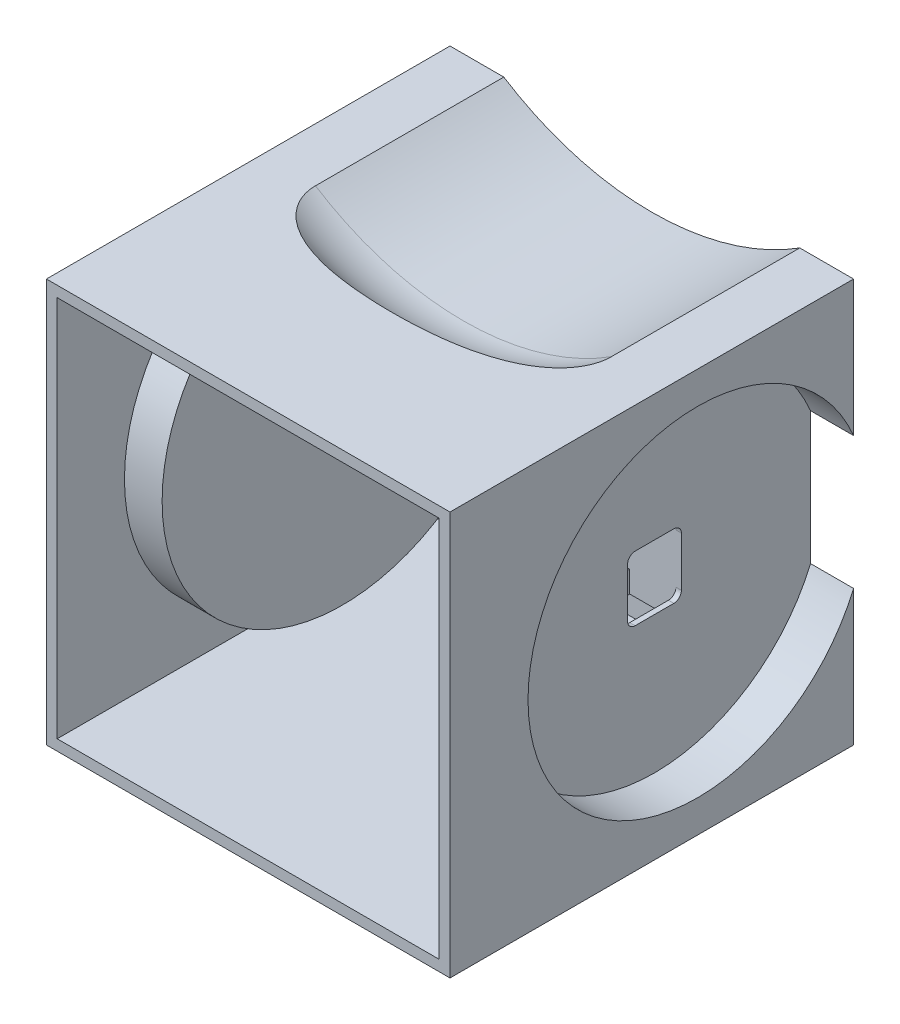
SolidWorks part; units mm, degrees
ref_plane "Plano frontal" through (0, 0, 0) normal (0, 0, 1) x (1, 0, 0)
ref_plane "Plano superior" through (0, 0, 0) normal (0, 1, 0) x (1, 0, 0)
ref_plane "Plano direito" through (0, 0, 0) normal (1, 0, 0) x (0, 0, -1)
sketch "Esboço1" plane through (0, 0, 0) normal (0, 0, 1) x (1, 0, 0)
  line L0 (-37.8091, -28.8009) -> (37.1909, -28.8009)
  line L1 (-37.8091, -28.8009) -> (-37.8091, 46.1991)
  line L2 (37.1909, -28.8009) -> (37.1909, 46.1991)
  line L3 (37.1909, 46.1991) -> (-37.8091, 46.1991)
  line L4 (-37.8091, 46.1991) -> (-27.8091, 46.1991)
  line L5 (37.1909, 46.1991) -> (27.1909, 46.1991)
  line L6 (-0.3091, 46.1991) -> (-0.3091, 38.1991)
  line L7 (-0.3091, 38.1991) -> (-0.3091, 36.1991)
  line L8 (-37.8091, 8.6991) -> (-35.8091, 8.6991)
  line L9 (-0.3091, -28.8009) -> (-0.3091, -26.8009)
  line L10 (31.7818, 46.1991) -> (31.7818, 44.1991)
  line L11 (37.1909, 41.0812) -> (35.1909, 41.0812)
  line L13 (-35.8091, -26.8009) -> (35.1909, -26.8009)
  line L14 (-35.8091, -26.8009) -> (-35.8091, 44.1991)
  line L15 (-35.8091, 44.1991) -> (35.1909, 44.1991)
  line L16 (35.1909, -26.8009) -> (35.1909, 44.1991)
  circle A0 centre (-0.3091, 89.4647) radius 51.2656
  circle A1 centre (-0.3091, 89.4647) radius 53.2656
  spline S0 degree 2 poles (-27.8091, 46.1991) (-0.3091, 30.1991) (27.1909, 46.1991) knots 0 0 0 1 1 1
  dimension "D7" = 102.5312
  dimension "D1" = 75
  dimension "D2" = 75
  dimension "D3" = 10
  dimension "D4" = 10
  dimension "D5" = 8
  dimension "D6" = 2
  dimension "D8" = 2
  dimension "D9" = 2
  dimension "D10" = 2
  dimension "D11" = 2
extrude "Ressalto-extrusão2" add sketch "Esboço1" along normal blind 50 contours A1 L4 L1 L8 L14 L15 | L3 A1 L15 A0 | L15 A1 L7 A0 | L7 A1 L15 A0 | L15 A1 L3 A0 | A1 L15 L10 L5 | L16 L11 L2 L3 L10 L15 | L16 L13 L9 L0 L2 L11 | L13 L14 L8 L1 L0 L9 region at (-37.2787, -10.0509, 0) region at (0.484, -27.8009, 0) region at (-36.2648, 29.8474, 0) region at (35.1096, 44.2634, 0) region at (-27.9997, 45.1797, 0) region at (-13.7006, 39.5358, 0) region at (30.3906, 44.9982, 0) region at (27.3815, 45.1797, 0) region at (13.0825, 39.5358, 0)
sketch "Esboço3" plane through (0, 0, 50) normal (0, 0, 1) x (1, 0, 0)
  line L0 (-37.8091, 46.1991) -> (-37.8091, -28.8009)
  line L1 (-37.8091, -28.8009) -> (37.1909, -28.8009)
  line L2 (37.1909, -28.8009) -> (37.1909, 46.1991)
  line L3 (37.1909, 46.1991) -> (-37.8091, 46.1991)
  line L4 (-35.8091, 44.1991) -> (-35.8091, -26.8009)
  line L5 (-35.8091, -26.8009) -> (35.1909, -26.8009)
  line L6 (35.1909, -26.8009) -> (35.1909, 44.1991)
  line L7 (35.1909, 44.1991) -> (-35.8091, 44.1991)
extrude "Ressalto-extrusão3" add sketch "Esboço3" along normal blind 25
sketch "Esboço4" plane through (0, 0, 50) normal (0, 0, 1) x (1, 0, 0)
  line L0 (-28.3849, 44.1991) -> (27.7667, 44.1991)
  circle A1 centre (-0.3091, 89.4647) radius 53.2656
  arc M3 (-28.3849, 44.1991) -> (27.7667, 44.1991) centre (-0.3091, 89.4647) ccw
  line M4 (27.7667, 44.1991) -> (23.7572, 44.1991)
  arc M5 (23.7572, 44.1991) -> (-24.3754, 44.1991) centre (-0.3091, 89.4647) cw
  line M6 (-24.3754, 44.1991) -> (-28.3849, 44.1991)
extrude "Ressalto-extrusão6" add sketch "Esboço4" along normal blind 2 contours L0 M5 | M6 M3 M4 M5 region at (-26.3801, 43.6319, 50) region at (-0.3091, 41.7866, 50)
fillet "Filete2" radius 15 1 edges at (-0.3091, 38.1991, 50)
sketch "Esboço5" plane through (0, 0, 0) normal (0, 0, -1) x (-1, 0, 0)
  line L0 (-27.1909, 46.1991) -> (-37.1909, 46.1991)
  line L1 (-37.1909, 46.1991) -> (-37.1909, -28.8009)
  line L2 (-37.1909, -28.8009) -> (37.8091, -28.8009)
  line L3 (37.8091, -28.8009) -> (37.8091, 46.1991)
  line L4 (37.8091, 46.1991) -> (27.8091, 46.1991)
  circle A0 centre (0.3091, 89.4647) radius 51.2656
  line M7 (28.3849, 44.1991) -> (35.8091, 44.1991)
  line M8 (35.8091, 44.1991) -> (35.8091, -26.8009)
  line M9 (35.8091, -26.8009) -> (-35.1909, -26.8009)
  line M10 (-35.1909, -26.8009) -> (-35.1909, 44.1991)
  line M11 (-35.1909, 44.1991) -> (-27.7667, 44.1991)
  arc M12 (-27.7667, 44.1991) -> (28.3849, 44.1991) centre (0.3091, 89.4647) ccw
extrude "Ressalto-extrusão7" add sketch "Esboço5" against normal blind 2 contours M7 M12 M11 M10 M9 M8 region at (-0.3091, 6.6255, 0)
sketch "Esboço6" plane through (-37.8091, 0, 0) normal (-1, 0, 0) x (0, 0, 1)
  line L0 (0, 46.1991) -> (0, -28.8009)
  line L3 (0, 8.6991) -> (-1, 8.6991)
  line L4 (-1, 8.6991) -> (59, 8.6991)
  circle A0 centre (29, 8.6991) radius 30
  circle A1 centre (29, 8.6991) radius 31.5
  line M5 (0, 46.1991) -> (0, -28.8009)
  dimension "D3" = 1.5
  dimension "D1" = 60
  dimension "D2" = 1
extrude "Corte-extrusão2" cut sketch "Esboço6" against normal blind 8 and the other way through all contours L4 A0 L0 | L0 A0 L4 | A1 L0 A0 M5 | L0 A1 A0 M5 | L3 A0 L0 | L0 A0 L3 region at (-37.8091, 38.7118, 35.101) region at (-37.8091, 8.6991, -1.203) region at (-37.8091, 21.4674, 29.1072) region at (-37.8091, 11.586, -0.4006) region at (-37.8091, -4.0692, 29.1072) region at (-37.8091, 5.8121, -0.4006)
sketch "Esboço7" plane through (35.1909, 0, 0) normal (-1, 0, 0) x (0, 0, 1)
  line L0 (2, 24.924) -> (2, -7.5259)
  circle A1 centre (29, 8.6991) radius 31.5
  line M2 (2, 44.1991) -> (2, -26.8009)
extrude "Corte-extrusão4" cut sketch "Esboço7" along normal blind 6 and the other way through all contours A1 M2 | A1 M2 region at (35.1909, 8.6991, 29.9434) region at (35.1909, 8.6991, 0.1885)
sketch "Esboço8" plane through (35.1909, 0, 0) normal (-1, 0, 0) x (0, 0, 1)
  line L0 (2, 24.924) -> (2, 28.5296)
  line L1 (2, -7.5259) -> (2, -11.1315)
  circle A0 centre (29, 8.6991) radius 31.5
  circle A1 centre (29, 8.6991) radius 33.5
  arc M2 (2, 24.924) -> (2, -7.5259) centre (29, 8.6991) cw
  line M3 (2, -7.5259) -> (2, -26.8009)
  line M7 (2, 44.1991) -> (2, 24.924)
  dimension "D1" = 2
extrude "Ressalto-extrusão8" add sketch "Esboço8" along normal blind 6 contours A1 M3 M7 M2 region at (35.1909, 26.7268, 2.9027)
sketch "Esboço9" plane through (-35.8091, 0, 0) normal (1, 0, 0) x (0, 0, -1)
  line L0 (-2, 24.924) -> (-2, 28.5296)
  line L1 (-2, -7.5259) -> (-2, -11.1315)
  line L2 (-2, -7.5259) -> (-2, -26.8009) construction
  circle A0 centre (-29, 8.6991) radius 31.5
  circle A1 centre (-29, 8.6991) radius 33.5
  arc M2 (-2, -7.5259) -> (-2, 24.924) centre (-29, 8.6991) cw
  line M3 (-2, 24.924) -> (-2, 44.1991)
  line M7 (-2, -26.8009) -> (-2, -7.5259)
  dimension "D1" = 2
extrude "Ressalto-extrusão9" add sketch "Esboço9" along normal blind 6 contours A1 M3 M7 M2 region at (-35.8091, 8.6991, 61.4027)
sketch "Esboço20" plane through (29.1909, 0, 0) normal (-1, 0, 0) x (0, 0, 1)
  line L0 (0, 20.9974) -> (0, -3.5993)
  line L1 (0, 20.9974) -> (0, 29.956)
  line L2 (0, -3.5993) -> (0, -14.1953)
  circle A0 centre (29, 8.6991) radius 33.5
  line M1 (2, -7.5259) -> (2, -11.1315)
  arc M2 (2, -11.1315) -> (2, 28.5296) centre (29, 8.6991) ccw
  line M3 (2, 28.5296) -> (2, 24.924)
  arc M4 (2, 24.924) -> (2, -7.5259) centre (29, 8.6991) cw
extrude "Ressalto-extrusão22" add sketch "Esboço20" along normal blind 1 contours M4 M1 M2 M3 | A0 L1 L0 L2 M3 M1 M4 region at (29.1909, 8.6991, 29.2565) region at (29.1909, 39.6748, 39.1531)
sketch "Esboço21" plane through (-29.8091, 0, 0) normal (1, 0, 0) x (0, 0, -1)
  line L0 (0, -2.839) -> (0, -10.7319)
  line L1 (0, 20.9974) -> (0, -3.5993) construction
  line L2 (0, 18.5479) -> (0, 28.8506)
  line L3 (0, 18.5479) -> (0, -2.839)
  circle A0 centre (-29, 8.6991) radius 33.5
  line M1 (-2, 24.924) -> (-2, 28.5296)
  arc M2 (-2, 28.5296) -> (-2, -11.1315) centre (-29, 8.6991) ccw
  line M3 (-2, -11.1315) -> (-2, -7.5259)
  arc M4 (-2, -7.5259) -> (-2, 24.924) centre (-29, 8.6991) cw
extrude "Ressalto-extrusão23" add sketch "Esboço21" along normal blind 1 contours M4 M1 M2 M3 | L2 A0 L0 L3 M1 M4 M3 region at (-29.8091, 8.6991, 29.2565) region at (-29.8091, 8.6991, 61.5973)
sketch "Esboço23" plane through (29.1909, 0, 0) normal (1, 0, 0) x (0, 0, -1)
  line L1 (-24, 2.6991) -> (-34, 2.6991)
  line L2 (-24, 2.6991) -> (-24, 14.6991)
  line L3 (-24, 14.6991) -> (-34, 14.6991)
  line L4 (-34, 2.6991) -> (-34, 14.6991)
  line L5 (-24, 2.6991) -> (-34, 14.6991) construction
  line L6 (-24, 14.6991) -> (-34, 2.6991) construction
  circle A0 centre (-29, 8.6991) radius 31.5
  dimension "D1" = 12
  dimension "D2" = 10
extrude "Corte-extrusão7" cut sketch "Esboço23" against normal through all contours L2 L1 L4 L3
sketch "Esboço24" plane through (0, 0, 2) normal (0, 0, 1) x (1, 0, 0)
  line L0 (-28.8091, 8.6991) -> (28.1909, 8.6991)
  line L1 (-28.8091, 28.5296) -> (-28.8091, -11.1315) construction
  line L2 (28.1909, -11.1315) -> (28.1909, 28.5296) construction
  line L4 (-28.8091, -1.3009) -> (28.1909, -1.3009)
  line L5 (-28.8091, -1.3009) -> (-28.8091, 18.6991)
  line L6 (-28.8091, 18.6991) -> (28.1909, 18.6991)
  line L7 (28.1909, -1.3009) -> (28.1909, 18.6991)
  line L8 (-28.8091, -1.3009) -> (28.1909, 18.6991) construction
  line L9 (-28.8091, 18.6991) -> (28.1909, -1.3009) construction
  point P6 (-0.3091, 8.6991)
  line M3 (-28.8091, 28.5296) -> (-28.8091, -11.1315)
  line M9 (28.1909, -11.1315) -> (28.1909, 28.5296)
  dimension "D1" = 20
extrude "Ressalto-extrusão24" add sketch "Esboço24" along normal blind 22 contours L6 L0 M3 M9 | L4 L0 M3 M9 region at (-0.3091, 13.6991, 2) region at (-0.3091, 3.6991, 2)
sketch "Esboço25" plane through (0, 0, 24) normal (0, 0, 1) x (1, 0, 0)
  line L0 (-0.3091, 18.6991) -> (-0.3091, -1.3009)
  line L1 (-28.8091, 18.6991) -> (28.1909, 18.6991) construction
  line L2 (-28.8091, -1.3009) -> (28.1909, -1.3009) construction
  line L3 (0.1909, 2.6991) -> (5.6949, 2.6991)
  line L4 (5.6949, 2.6991) -> (5.6949, 14.6991)
  line L5 (-0.3091, 8.6991) -> (0.1909, 8.6991)
  line L6 (0.1909, 14.6991) -> (0.1909, 2.6991)
  line L7 (0.1909, 14.6991) -> (0.1909, 2.6991)
  line L8 (0.1909, 14.6991) -> (21.6909, 14.6991)
  line L9 (0.1909, 2.6991) -> (21.6909, 2.6991)
  line L10 (21.6909, 14.6991) -> (21.6909, 2.6991)
  line L11 (21.6909, 2.6991) -> (21.6909, 14.6991)
  line L12 (21.6909, 2.6991) -> (30.6909, 2.6991)
  line L13 (21.6909, 14.6991) -> (30.6909, 14.6991)
  line L14 (30.6909, 2.6991) -> (30.6909, 14.6991)
  line L15 (-0.3091, 8.6991) -> (-0.8091, 8.6991)
  line L16 (-0.8091, 14.6991) -> (-0.8091, 2.6991)
  line L17 (-0.8091, 14.6991) -> (-0.8091, 2.6991)
  line L18 (-0.8091, 14.6991) -> (-22.3091, 14.6991)
  line L19 (-0.8091, 2.6991) -> (-22.3091, 2.6991)
  line L20 (-22.3091, 14.6991) -> (-22.3091, 2.6991)
  line L21 (-22.3091, 14.6991) -> (-22.3091, 2.6991)
  line L22 (-22.3091, 14.6991) -> (-31.3091, 14.6991)
  line L23 (-22.3091, 2.6991) -> (-31.3091, 2.6991)
  line L24 (-31.3091, 14.6991) -> (-31.3091, 2.6991)
  line L25 (-0.8091, 2.6991) -> (-6.3091, 2.6991)
  line L26 (-6.3091, 2.6991) -> (-6.3091, 14.6991)
  line L32 (-28.8091, -1.3009) -> (28.1909, -1.3009) construction
  line L37 (-28.8091, 18.6991) -> (28.1909, 18.6991) construction
  line L46 (5.6949, 14.6991) -> (19.5949, 14.6991)
  line L47 (5.6949, 14.6991) -> (5.6949, 18.6991)
  line L48 (5.6949, 18.6991) -> (19.5949, 18.6991)
  line L49 (19.5949, 14.6991) -> (19.5949, 18.6991)
  line L50 (5.6949, 2.6991) -> (19.5949, 2.6991)
  line L51 (5.6949, 2.6991) -> (5.6949, -1.3009)
  line L52 (5.6949, -1.3009) -> (19.5949, -1.3009)
  line L53 (19.5949, 2.6991) -> (19.5949, -1.3009)
  line L54 (-6.3091, 14.6991) -> (-20.2091, 14.6991)
  line L55 (-6.3091, 14.6991) -> (-6.3091, 18.6991)
  line L56 (-6.3091, 18.6991) -> (-20.2091, 18.6991)
  line L57 (-20.2091, 14.6991) -> (-20.2091, 18.6991)
  line L59 (-6.3091, 2.6991) -> (-20.2091, 2.6991)
  line L60 (-6.3091, 2.6991) -> (-6.3091, -1.3009)
  line L61 (-6.3091, -1.3009) -> (-20.2091, -1.3009)
  line L62 (-20.2091, 2.6991) -> (-20.2091, -1.3009)
  point P14 (0.1909, 8.6991)
  point P22 (-0.8091, 8.6991)
  line M3 (28.1909, 18.6991) -> (-28.8091, 18.6991)
  line M9 (-28.8091, -1.3009) -> (28.1909, -1.3009)
  dimension "D1" = 0.5
  dimension "D2" = 12
  dimension "D3" = 21.5
  dimension "D4" = 9
  dimension "D5" = 0.5
  dimension "D6" = 12
  dimension "D7" = 21.5
  dimension "D8" = 9
  dimension "D9" = 5.5
  dimension "D10" = 5.504
  dimension "D11" = 13.9
  dimension "D12" = 13.9
  dimension "D13" = 13.9
extrude "Ressalto-extrusão25" add sketch "Esboço25" along normal blind 5 contours L19 M9 | L9 M9 | L8 M3 | L18 L54 M3 region at (12.6449, 16.6991, 24) region at (-13.2591, 16.6991, 24) region at (-13.2591, 0.6991, 24) region at (12.6449, 0.6991, 24)
fillet "Filete4" radius 1.4 4 edges at (28.6909, 14.6991, 34) (28.6909, 14.6991, 24) (28.6909, 2.6991, 34) (28.6909, 2.6991, 24)
fillet "Filete5" radius 1.4 4 edges at (-29.3091, 14.6991, 24) (-29.3091, 2.6991, 24) (-29.3091, 2.6991, 34) (-29.3091, 14.6991, 34)
